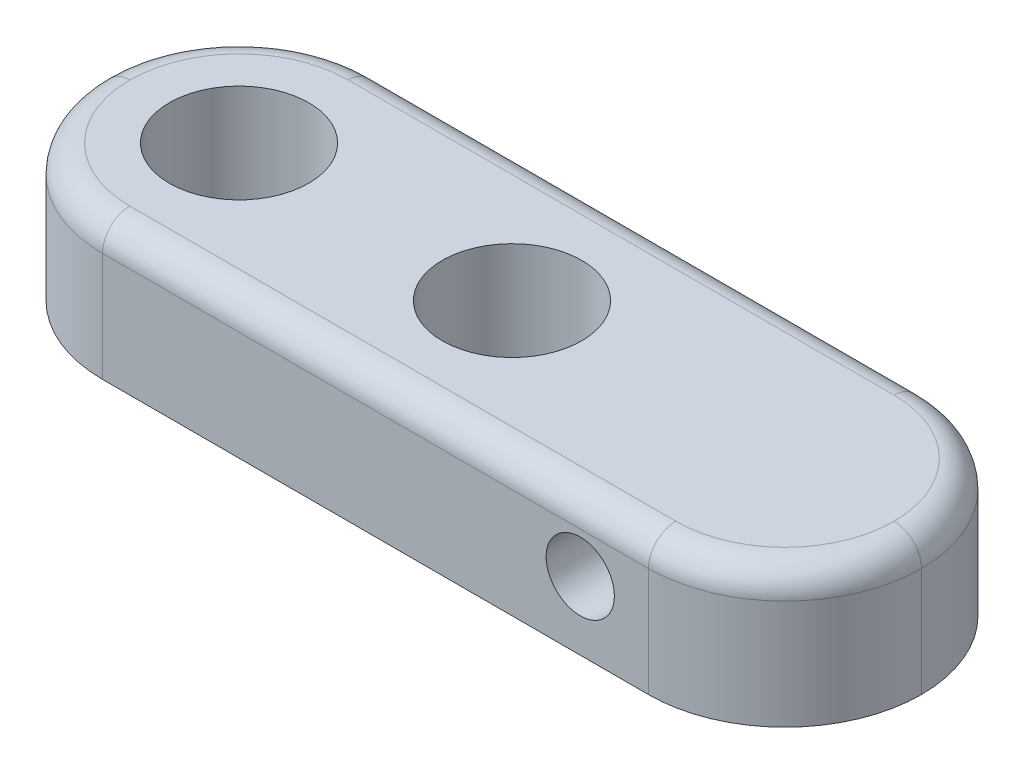
SolidWorks part; units mm, degrees
ref_plane "Front Plane" through (0, 0, 0) normal (0, 0, 1) x (1, 0, 0)
ref_plane "Top Plane" through (0, 0, 0) normal (0, 1, 0) x (1, 0, 0)
ref_plane "Right Plane" through (0, 0, 0) normal (1, 0, 0) x (0, 0, -1)
sketch "Sketch1" plane through (0, 0, 0) normal (0, 1, 0) x (1, 0, 0)
  line L1 (-5, 5) -> (25, 5)
  line L2 (-5, 5) -> (-5, -5)
  line L3 (-5, -5) -> (25, -5)
  line L4 (25, 5) -> (25, -5)
  circle A0 centre (0, 0) radius 2.555
  circle A1 centre (10, 0) radius 2.555
  point P5 (-5, 0)
  dimension "D1" = 5.11
  dimension "D2" = 5.11
  dimension "D4" = 5
  dimension "D3" = 10
  dimension "D5" = 10
  dimension "D6" = 30
extrude "Boss-Extrude1" add sketch "Sketch1" along normal blind 5
sketch "Sketch2" plane through (0, 0, 5) normal (0, 0, 1) x (1, 0, 0)
  line L0 (25, 5) -> (25, 0) construction
  line L1 (-5, 5) -> (25, 5) construction
  line L2 (18.625, 4.4486) -> (16.375, 4.4486)
  line L3 (16.375, 4.4486) -> (15.25, 2.5)
  line L4 (15.25, 2.5) -> (16.375, 0.5514)
  line L5 (16.375, 0.5514) -> (18.625, 0.5514)
  line L6 (18.625, 0.5514) -> (19.75, 2.5)
  line L7 (19.75, 2.5) -> (18.625, 4.4486)
  circle A0 centre (17.5, 2.5) radius 1.25
  circle A1 centre (17.5, 2.5) radius 1.9486 construction
  point P4 (25, 2.5)
  dimension "D2" = 2.5
  dimension "D1" = 7.5
  dimension "D3" = 2.25
extrude "Cut-Extrude1" cut sketch "Sketch2" against normal through all contours A0 region at (17.5, 2.5, 5)
extrude "Cut-Extrude2" cut sketch "Sketch2<3>" along normal blind 5 from surface starting at face at (18.75, 2.5, -5)
sketch "Sketch2<3>" plane through (0, 0, 5) normal (0, 0, 1) x (1, 0, 0) same geometry as "Sketch2"
fillet "Fillet1" radius 5 4 edges at (-5, 2.5, -5) (-5, 2.5, 5) (25, 2.5, -5) (25, 2.5, 5)
fillet "Fillet2" radius 1 6 edges at (-3.5355, 5, 3.5355) (-3.5355, 5, -3.5355) (10, 5, -5) (23.5355, 5, -3.5355) (23.5355, 5, 3.5355) (10, 5, 5)
